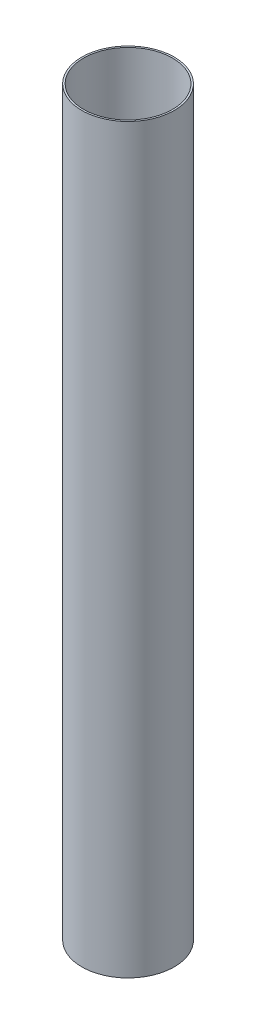
SolidWorks part; units mm, degrees
material "S-Glass Fiber"
ref_plane "Front Plane" through (0, 0, 0) normal (0, 0, 1) x (1, 0, 0)
ref_plane "Top Plane" through (0, 0, 0) normal (0, 1, 0) x (1, 0, 0)
ref_plane "Right Plane" through (0, 0, 0) normal (1, 0, 0) x (0, 0, -1)
sketch "Sketch4" plane through (0, 0, 0) normal (0, 1, 0) x (1, 0, 0)
  circle A0 centre (-10.0305, 2.7128) radius 39.6
  circle A1 centre (-10.0305, 2.7128) radius 38.1
  point P2 (0, 0)
  point P3 (0, 0)
  point P4 (0, 0)
  point P5 (0, 0)
  dimension "D1" = 79.2
  dimension "D2" = 76.2
extrude "Boss-Extrude2" add sketch "Sketch4" along normal blind 635
